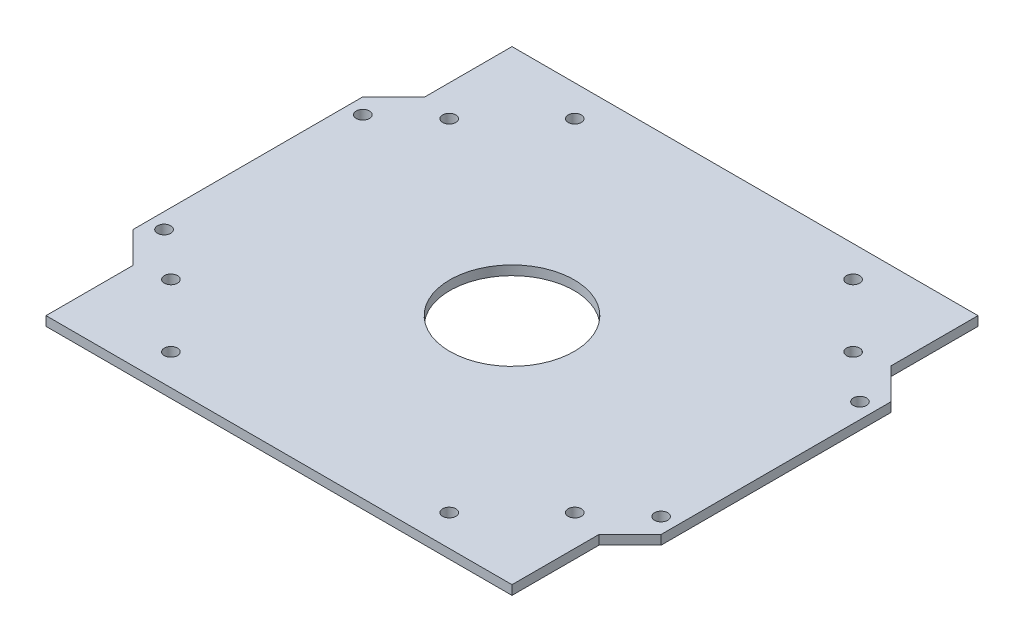
SolidWorks part; units mm, degrees
ref_plane "Front Plane" through (0, 0, 0) normal (0, 0, 1) x (1, 0, 0)
ref_plane "Top Plane" through (0, 0, 0) normal (0, 1, 0) x (1, 0, 0)
ref_plane "Right Plane" through (0, 0, 0) normal (1, 0, 0) x (0, 0, -1)
sketch "Sketch1" plane through (0, 0, 0) normal (0, 1, 0) x (1, 0, 0)
  line L1 (-75, -75) -> (75, -75)
  line L2 (-75, -75) -> (-75, 75)
  line L3 (-75, 75) -> (75, 75)
  line L4 (75, -75) -> (75, 75)
  line L5 (-75, -75) -> (75, 75) construction
  line L6 (-75, 75) -> (75, -75) construction
  point P0 (0, 0)
  dimension "D1" = 150
  dimension "D2" = 150
extrude "Boss-Extrude1" add sketch "Sketch1" along normal blind 3
sketch "Sketch2" plane through (0, 3, 0) normal (0, 1, 0) x (1, 0, 0)
  line L0 (75, 75) -> (55, 75) construction
  line L1 (-75, 75) -> (-55, 75) construction
  line L2 (-75, 75) -> (-75, 55) construction
  line L3 (-75, 55) -> (-55, 55) construction
  line L4 (-55, 75) -> (-55, 55) construction
  line L5 (75, 75) -> (75, 55) construction
  line L6 (75, 55) -> (55, 55) construction
  line L7 (55, 75) -> (55, 55) construction
  line L8 (75, -75) -> (75, -55) construction
  line L9 (75, -75) -> (55, -75) construction
  line L10 (55, -75) -> (55, -55) construction
  line L11 (75, -55) -> (55, -55) construction
  line L12 (-75, -75) -> (-55, -75) construction
  line L13 (-75, -75) -> (-75, -55) construction
  line L14 (-75, -55) -> (-55, -55) construction
  line L15 (-55, -75) -> (-55, -55) construction
  line L16 (-65, -75) -> (-65, 75) construction
  line L17 (-75, 0) -> (75, 0) construction
  line L18 (-75, 75) -> (-75, -75) construction
  line L19 (75, -75) -> (75, 75) construction
  circle A0 centre (-65, -44.8) radius 2.125
  circle A1 centre (-65, 44.8) radius 2.125
  circle A2 centre (-44.8, 65) radius 2.125
  circle A3 centre (44.8, 65) radius 2.125
  circle A4 centre (65, 44.8) radius 2.125
  circle A5 centre (65, -44.8) radius 2.125
  circle A6 centre (44.8, -65) radius 2.125
  circle A7 centre (-44.8, -65) radius 2.125
  circle A8 centre (0, 0) radius 20
  point P44 (0, 0)
  dimension "D4" = 4.25
  dimension "40" = 40
  dimension "D1" = 20
  dimension "D2" = 20
  dimension "D5" = 10.2
  dimension "D3" = 4
  dimension "D6" = 4
extrude "Cut-Extrude3" cut sketch "Sketch2" against normal through all
sketch "Sketch3" plane through (0, 3, 0) normal (0, 1, 0) x (1, 0, 0)
  line L0 (-85, 0) -> (-75, 0) construction
  line L1 (-85, -37) -> (-75, -37)
  line L2 (-85, -37) -> (-85, 37)
  line L3 (-85, 37) -> (-75, 37)
  line L5 (0, 75) -> (0, -75) construction
  line L6 (75, 75) -> (-75, 75) construction
  line L7 (-75, -75) -> (75, -75) construction
  line L8 (-75, -37) -> (-75, 37)
  line L9 (-75, 75) -> (-75, -75) construction
  line L10 (85, -37) -> (85, 37)
  line L11 (85, 37) -> (75, 37)
  line L12 (75, -37) -> (75, 37)
  line L13 (85, -37) -> (75, -37)
  circle A0 centre (-80, 32) radius 2.125
  circle A1 centre (-80, -32) radius 2.125
  circle A2 centre (80, -32) radius 2.125
  circle A3 centre (80, 32) radius 2.125
  point P0 (0, 0)
  dimension "D1" = 4.25
  dimension "D2" = 32
  dimension "D3" = 5
  dimension "D4" = 80
  dimension "D5" = 5
  dimension "D6" = 0
extrude "Boss-Extrude2" add sketch "Sketch3" against normal up to surface (3 mm away) up to face at (-65, 0, -46.925)
sketch "Sketch4" plane through (0, 3, 0) normal (0, 1, 0) x (1, 0, 0)
  line L0 (-85, 37) -> (-75, 47)
  line L1 (-75, 75) -> (-75, 37) construction
  line L2 (-75, 47) -> (-75, 37)
  line L3 (-75, 37) -> (-85, 37)
  line L4 (0, 75) -> (0, -75) construction
  line L5 (75, 75) -> (-75, 75) construction
  line L6 (-75, -75) -> (75, -75) construction
  line L7 (-85, 0) -> (85, 0) construction
  line L8 (-85, 37) -> (-85, -37) construction
  line L9 (85, -37) -> (85, 37) construction
  line L10 (75, 47) -> (75, 37)
  line L11 (85, 37) -> (75, 47)
  line L12 (75, 37) -> (85, 37)
  line L13 (85, -37) -> (75, -47)
  line L14 (75, -37) -> (85, -37)
  line L15 (75, -47) -> (75, -37)
  line L16 (-75, -47) -> (-75, -37)
  line L17 (-85, -37) -> (-75, -47)
  line L18 (-75, -37) -> (-85, -37)
  dimension "D1" = 10
extrude "Boss-Extrude3" add sketch "Sketch4" against normal up to surface (3 mm away) contours L10 L12 L11 | L3 L0 L2 | L13 L15 L14 | L16 L18 L17 up to face at (-65, 0, -46.925)
